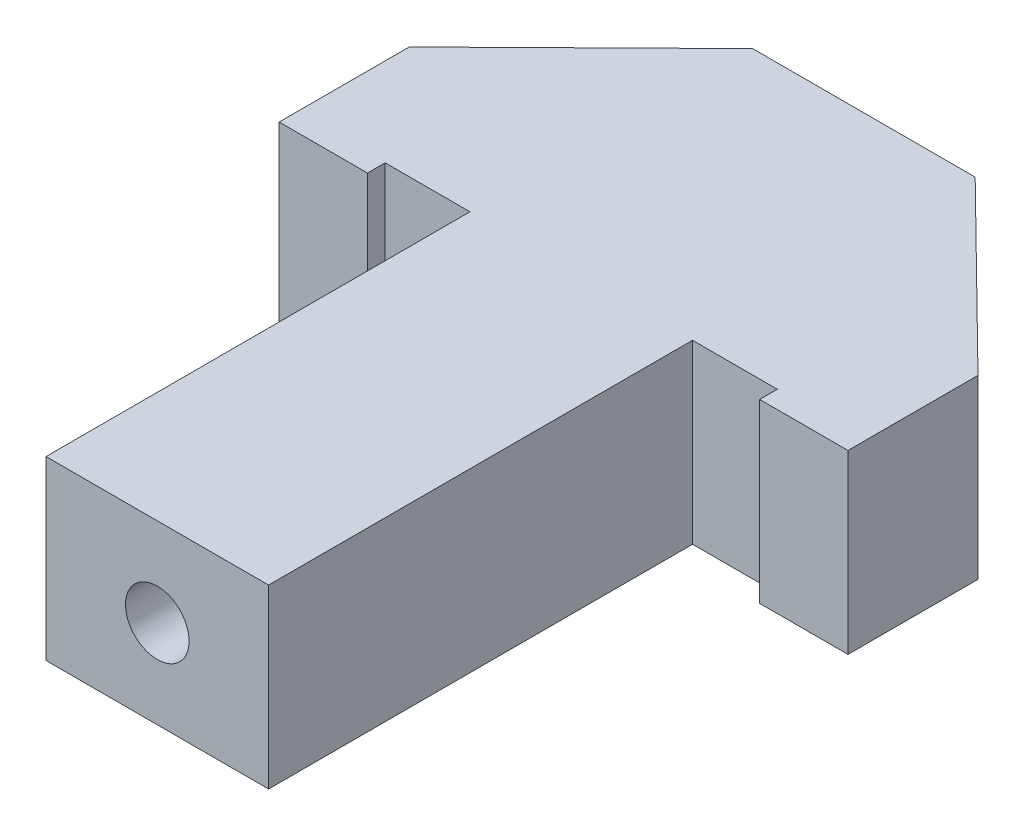
SolidWorks part; units mm, degrees
material "AISI 304"
ref_plane "Front Plane" through (0, 0, 0) normal (0, 0, 1) x (1, 0, 0)
ref_plane "Top Plane" through (0, 0, 0) normal (0, 1, 0) x (1, 0, 0)
ref_plane "Right Plane" through (0, 0, 0) normal (1, 0, 0) x (0, 0, -1)
sketch "Sketch1" plane through (0, 0, 0) normal (0, 1, 0) x (1, 0, 0)
  line L3 (0, 0) -> (4.1323, 0)
  line L4 (0, 0) -> (-2.0907, 0)
  line L5 (-2.0907, 0) -> (-2.0907, 4.0386)
  line L6 (-2.0907, 4.0386) -> (4.1323, 10.16)
  line L7 (4.1323, 10.16) -> (8.1328, 10.16)
  line L8 (8.1328, 10.16) -> (8.1328, -15.24)
  line L9 (4.1323, 0) -> (4.1323, -15.24)
  line L18 (4.1323, -15.24) -> (8.1328, -15.24)
  dimension "D1" = 4.0005
  dimension "D2" = 15.24
  dimension "D3" = 6.223
  dimension "D6" = 4.0005
  dimension "D7" = 25.4
  dimension "D8" = 4.0386
extrude "Boss-Extrude1" add sketch "Sketch1" along normal blind 6.35
ref_plane "Plane1" through (8.1328, 0, 0) normal (1, 0, 0) x (0, 0, -1)
mirror "Mirror1" about plane through (8.1328, 0, 0) normal (1, 0, 0) of "Boss-Extrude1"
sketch "Sketch3" plane through (0, 0, 0) normal (0, -1, 0) x (-1, 0, 0)
  line L0 (-18.3563, 0) -> (-12.1333, 0) construction
  line L1 (-15.1813, 0) -> (-18.3563, 0)
  line L2 (-15.1813, 0) -> (-15.1813, -0.635)
  line L3 (-15.1813, -0.635) -> (-18.3563, -0.635)
  line L4 (-18.3563, 0) -> (-18.3563, -0.635)
  dimension "D1" = 0.635
  dimension "D2" = 3.175
extrude "Boss-Extrude2" add sketch "Sketch3" against normal up to surface (6.35 mm away) up to face at (8.1328, 6.35, 0.2083)
mirror "Mirror2" about plane through (8.1328, 0, 0) normal (1, 0, 0) of "Boss-Extrude2"
sketch "Sketch4" plane through (0, 0, -10.16) normal (0, 0, -1) x (-1, 0, 0)
  line L0 (-12.1333, 0) -> (-4.1323, 0) construction
  line L1 (-12.1333, 6.35) -> (-12.1333, 0) construction
  circle A0 centre (-8.1328, 3.175) radius 1.143
  dimension "D1" = 2.286
  dimension "D2" = 3.175
  dimension "D3" = 4.0005
extrude "Cut-Extrude1" cut sketch "Sketch4" against normal blind 50.8
sketch "Sketch5" plane through (0, 0, -10.16) normal (0, 0, -1) x (-1, 0, 0)
  circle A0 centre (-8.1328, 3.175) radius 2.9
  circle A1 centre (-8.1328, 3.175) radius 1.143 construction
  dimension "D1" = 5.8
extrude "Cut-Extrude2" cut sketch "Sketch5" against normal blind 3.55
